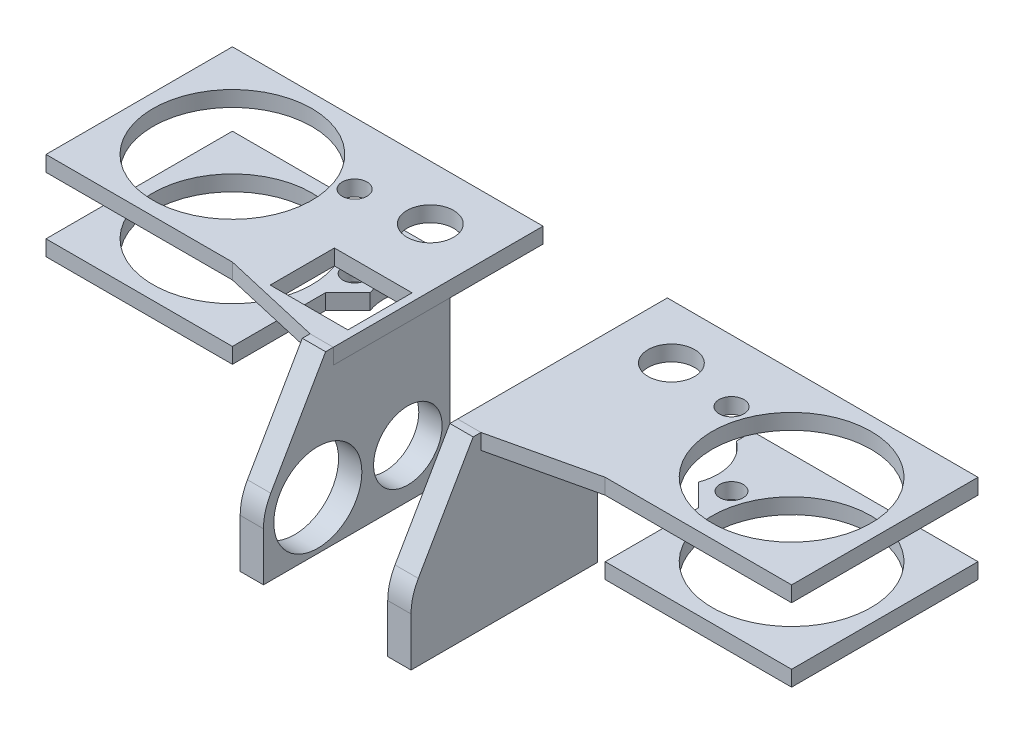
SolidWorks part; units mm, degrees
material "Alum Plate"
ref_plane "Front Plane" through (0, 0, 0) normal (0, 0, 1) x (1, 0, 0)
ref_plane "Top Plane" through (0, 0, 0) normal (0, 1, 0) x (1, 0, 0)
ref_plane "Right Plane" through (0, 0, 0) normal (1, 0, 0) x (0, 0, -1)
sketch "Sketch1" plane through (0, 0, 0) normal (0, 1, 0) x (1, 0, 0)
  line L0 (0, 0) -> (114.3, 0) construction
  line L1 (-114.3, 0) -> (0, 0) construction
  line L3 (-9.525, 158.75) -> (-3.175, 158.75)
  line L4 (-9.525, 158.75) -> (-9.525, 44.45)
  line L5 (-9.525, 44.45) -> (-3.175, 44.45)
  line L6 (-3.175, 158.75) -> (-3.175, 44.45)
  line L7 (-9.525, 158.75) -> (-3.175, 44.45) construction
  line L8 (-9.525, 44.45) -> (-3.175, 158.75) construction
  line L14 (-152.4, -76.2) -> (152.4, -76.2)
  line L18 (-114.3, 0) -> (-49.2756, 15.875) construction
  line L19 (49.2756, 15.875) -> (114.3, 0) construction
  line L20 (-25.4, 38.1) -> (0, 38.1) construction
  line L21 (-6.35, 101.6) -> (0, 101.6)
  line L29 (0, 0) -> (0, -25.4) construction
  line L30 (-114.3, 0) -> (-77.0346, 12.7) construction
  line L43 (-77.0346, 12.7) -> (-49.2756, 15.875) construction
  line L44 (49.2756, 15.875) -> (77.0346, 12.7) construction
  line L55 (77.0346, 12.7) -> (114.3, 0) construction
  line L69 (-152.4, -76.2) -> (-152.4, 38.1)
  line L70 (-152.4, 38.1) -> (152.4, 38.1)
  line L71 (152.4, -76.2) -> (152.4, 38.1)
  line L78 (0, 101.6) -> (0, -25.4)
  line L79 (0, -25.4) -> (0, -152.4) construction
  line L80 (-9.525, -209.55) -> (-3.175, -209.55) construction
  line L81 (-9.525, -209.55) -> (-9.525, -95.25) construction
  line L82 (-9.525, -95.25) -> (-3.175, -95.25) construction
  line L83 (-3.175, -209.55) -> (-3.175, -95.25) construction
  line L84 (-9.525, -209.55) -> (-3.175, -95.25) construction
  line L85 (-9.525, -95.25) -> (-3.175, -209.55) construction
  line L86 (0, -152.4) -> (-6.35, -152.4) construction
  line L87 (-34.925, -76.2) -> (-25.4, -76.2)
  line L88 (-34.925, -76.2) -> (-34.925, 38.1)
  line L89 (-34.925, 38.1) -> (-25.4, 38.1)
  line L90 (-25.4, -76.2) -> (-25.4, 38.1)
  line L91 (34.925, -76.2) -> (25.4, -76.2)
  line L92 (34.925, -76.2) -> (34.925, 38.1)
  line L93 (34.925, 38.1) -> (25.4, 38.1)
  line L94 (25.4, -76.2) -> (25.4, 38.1)
  line L95 (0, 38.1) -> (25.4, 38.1) construction
  circle A0 centre (-114.3, 0) radius 32.5
  circle A1 centre (-114.3, 0) radius 25
  circle A2 centre (114.3, 0) radius 32.5
  circle A3 centre (114.3, 0) radius 25
  circle A4 centre (-49.2756, 15.875) radius 17.5006
  circle A5 centre (49.2756, 15.875) radius 17.5006
  circle A6 centre (-77.0346, 12.7) radius 22.86
  circle A7 centre (77.0346, 12.7) radius 22.86
  point P8 (-6.35, 101.6)
  point P21 (114.3, 32.5)
  point P25 (49.2756, 33.3756)
  point P29 (49.2756, -1.6256)
  point P31 (0, -76.2)
  point P32 (-6.35, -152.4)
  point P62 (146.8, 0)
  dimension "D1" = 50
  dimension "D2" = 65
  dimension "D8" = 35.0012
  dimension "D11" = 127
  dimension "D12" = 63.5
  dimension "D17" = 45.72
  dimension "D3" = 114.3
  dimension "D4" = 6.35
  dimension "D5" = 228.6
  dimension "D6" = 38.1
  dimension "D7" = 38.1
  dimension "D9" = 114.3
  dimension "D10" = 9.525
  dimension "D13" = 9.525
  dimension "D14" = 50.8
  dimension "D15" = 27.94
  dimension "D16" = 39.37
  dimension "D18" = 22.225
  dimension "D19" = 25.4
sketch "Sketch2" plane through (0, 0, 0) normal (1, 0, 0) x (0, 0, -1)
  line L0 (0, 22.225) -> (0, 49.825) construction
  line L1 (-32.5, 53.325) -> (32.5, 53.325)
  line L2 (-32.5, 53.325) -> (-32.5, 46.325)
  line L3 (-32.5, 46.325) -> (32.5, 46.325)
  line L4 (32.5, 53.325) -> (32.5, 46.325)
  line L5 (-32.5, 53.325) -> (32.5, 46.325) construction
  line L6 (-32.5, 46.325) -> (32.5, 53.325) construction
  line L7 (-32.5, 82.55) -> (32.5, 82.55)
  line L8 (-32.5, 82.55) -> (-32.5, 75.55)
  line L9 (-32.5, 75.55) -> (32.5, 75.55)
  line L10 (32.5, 82.55) -> (32.5, 75.55)
  line L11 (-32.5, 82.55) -> (32.5, 75.55) construction
  line L12 (-32.5, 75.55) -> (32.5, 82.55) construction
  line L13 (-25.8191, 0) -> (33.9817, 0) construction
  line L14 (-25.4, 63.5) -> (-152.4, 63.5)
  line L15 (-76.2, 82.55) -> (38.1, 82.55)
  line L16 (-76.2, 82.55) -> (-76.2, 46.325)
  line L17 (-76.2, 46.325) -> (38.1, 46.325)
  line L18 (38.1, 82.55) -> (38.1, 46.325)
  line L19 (-17.175, 32.5662) -> (-53.975, 32.5662) construction
  line L20 (-53.975, 32.5662) -> (-25.4, 63.5) construction
  line L21 (101.6, 0) -> (-25.4, 0) construction
  line L22 (-76.2, 76.2) -> (38.1, 76.2)
  line L23 (-76.2, 52.675) -> (38.1, 52.675)
  line L24 (-17.175, 32.5662) -> (-25.4, 63.5) construction
  line L25 (-3.175, 32.5662) -> (-3.175, 75.55) construction
  line L32 (-76.2, 12.7) -> (38.1, 12.7)
  line L33 (-76.2, 12.7) -> (-76.2, 9.525)
  line L38 (-76.2, 9.525) -> (38.1, 9.525)
  line L39 (38.1, 12.7) -> (38.1, 9.525)
  line L40 (-1.6256, 31.6992) -> (33.3756, 31.6992)
  line L41 (-1.6256, 31.6992) -> (-1.6256, 76.2)
  line L42 (-1.6256, 76.2) -> (33.3756, 76.2)
  line L43 (33.3756, 31.6992) -> (33.3756, 76.2)
  line L44 (-1.6256, 31.6992) -> (33.3756, 76.2) construction
  line L45 (-1.6256, 76.2) -> (33.3756, 31.6992) construction
  line L46 (-38.1, 82.55) -> (-38.1, 46.325)
  line L47 (-38.1, 64.4375) -> (0, 64.4375) construction
  line L48 (0, 64.4375) -> (38.1, 64.4375) construction
  line L49 (-76.2, 12.7) -> (38.1, 9.525) construction
  line L50 (-76.2, 9.525) -> (38.1, 12.7) construction
  circle A0 centre (0, 22.225) radius 22.225
  circle A1 centre (-25.4, 63.5) radius 18.0086
  circle A2 centre (-17.175, 32.5662) radius 14
  circle A3 centre (-152.4, 63.5) radius 57.15
  circle A4 centre (-25.4, 63.5) radius 4.7625
  circle A5 centre (-53.975, 32.5662) radius 18
  point P2 (0, 49.825)
  point P8 (0, 79.05)
  point P16 (-35.975, 32.5662)
  point P28 (-71.975, 32.5662)
  point P32 (15.875, 53.9496)
  point P34 (-209.55, 63.5)
  point P35 (-31.175, 32.5662)
  point P36 (-3.175, 32.5662)
  point P37 (-7.3914, 63.5)
  point P38 (-43.4086, 63.5)
  point P57 (-19.05, 11.1125)
  dimension "D1" = 44.45
  dimension "D8" = 36.0172
  dimension "D2" = 28
  dimension "D11" = 9.525
  dimension "D12" = 36
  dimension "D3" = 7
  dimension "D4" = 82.55
  dimension "D5" = 22.225
  dimension "D6" = 6.35
  dimension "D7" = 6.35
  dimension "D9" = 63.5
  dimension "D10" = 44.5008
  dimension "D13" = 19.05
  dimension "D14" = 28.575
  dimension "D15" = 3.175
  dimension "D16" = 50.8
sketch "Sketch5" plane through (0, 0, 0) normal (0, 1, 0) x (1, 0, 0)
  line L0 (-34.925, -76.2) -> (-34.925, 38.1) construction
  line L1 (-60.071, -3.175) -> (-28.575, -3.175)
  line L2 (-60.071, -3.175) -> (-60.071, -31.175)
  line L3 (-60.071, -31.175) -> (-28.575, -31.175)
  line L4 (-28.575, -3.175) -> (-28.575, -31.175)
  line L5 (-60.071, -3.175) -> (-28.575, -31.175) construction
  line L6 (-60.071, -31.175) -> (-28.575, -3.175) construction
  line L7 (-74.93, -35.975) -> (-34.925, -35.975)
  line L8 (-74.93, -35.975) -> (-74.93, -71.975)
  line L9 (-74.93, -71.975) -> (-34.925, -71.975)
  line L10 (-34.925, -35.975) -> (-34.925, -71.975)
  line L11 (-74.93, -35.975) -> (-34.925, -71.975) construction
  line L12 (-74.93, -71.975) -> (-34.925, -35.975) construction
  line L13 (-60.071, -7.3914) -> (-20.066, -7.3914)
  line L14 (-60.071, -7.3914) -> (-60.071, -43.4086)
  line L15 (-60.071, -43.4086) -> (-20.066, -43.4086)
  line L16 (-20.066, -7.3914) -> (-20.066, -43.4086)
  line L17 (-60.071, -7.3914) -> (-20.066, -43.4086) construction
  line L18 (-60.071, -43.4086) -> (-20.066, -7.3914) construction
  line L20 (-25.4, -76.2) -> (-25.4, 38.1) construction
  point P0 (-44.323, -17.175)
  point P5 (-54.9275, -53.975)
  point P10 (-40.0685, -25.4)
  point P15 (-25.4, -3.175)
  point P16 (-29.3548, -3.175)
  dimension "D1" = 3.175
  dimension "D2" = 31.496
  dimension "D5" = 40.005
  dimension "D6" = 40.005
ref_plane "Plane1" through (0, 76.2, 0) normal (0, 1, 0) x (1, 0, 0)
ref_plane "Plane2" through (0, 52.675, 0) normal (0, -1, 0) x (-1, 0, 0)
ref_plane "Plane3" through (25.4, 0, 0) normal (1, 0, 0) x (0, 0, -1)
sketch "Sketch6" plane through (25.4, 0, 0) normal (1, 0, 0) x (0, 0, -1)
  line L2 (-73.2267, 43.6713) -> (-50.8, 82.55)
  line L3 (-76.2, 82.55) -> (38.1, 82.55) construction
  line L4 (-50.8, 82.55) -> (-47.625, 82.55)
  line L5 (-47.625, 82.55) -> (-47.625, 76.2)
  line L6 (-76.2, 76.2) -> (38.1, 76.2) construction
  line L7 (-47.625, 76.2) -> (0, 76.2)
  line L8 (0, 76.2) -> (0, 12.7)
  line L10 (-76.2, 12.7) -> (38.1, 12.7) construction
  line L11 (-76.2, 12.7) -> (-76.2, 32.5662)
  line L12 (-76.2, 12.7) -> (0, 12.7)
  arc A3 (-76.2, 32.5662) -> (-73.2267, 43.6713) centre (-53.975, 32.5662) cw
  point P7 (-73.8749, 40.41)
  dimension "D1" = 25.4
  dimension "D2" = 22.225
  dimension "D3" = 3.175
extrude "Boss-Extrude1" add sketch "Sketch6" along normal up to vertex (9.525 mm away) up to point (34.925, 0, -38.1)
sketch "Sketch7" plane through (0, 76.2, 0) normal (0, 1, 0) x (1, 0, 0)
  line L0 (25.4, -47.625) -> (34.925, -47.625)
  line L2 (152.4, -76.2) -> (152.4, 38.1) construction
  line L3 (152.4, -38.1) -> (152.4, 38.1)
  line L4 (152.4, 38.1) -> (25.4, 38.1)
  line L5 (25.4, 38.1) -> (25.4, -47.625)
  line L6 (152.4, -38.1) -> (76.2, -38.1)
  line L7 (76.2, -38.1) -> (34.925, -47.625)
  line L8 (114.3, 38.1) -> (114.3, 0) construction
  line L9 (114.3, 0) -> (114.3, -38.1) construction
  circle A0 centre (114.3, 0) radius 32.5 construction
  circle A1 centre (114.3, 0) radius 32.5
  circle A2 centre (77.0346, 12.7) radius 5.08
  circle A3 centre (49.2756, 15.875) radius 9.525
  dimension "D1" = 10.16
  dimension "D2" = 19.05
extrude "Boss-Extrude2" add sketch "Sketch7" along normal up to surface (6.35 mm away) separate body up to face at (30.1625, 82.55, 49.2125)
sketch "Sketch8" plane through (0, 52.675, 0) normal (0, -1, 0) x (-1, 0, 0)
  line L0 (-60.325, 31.3932) -> (-60.325, 38.1)
  line L1 (-76.2, -38.1) -> (-152.4, -38.1)
  line L2 (-76.2, -38.1) -> (-76.2, 38.1) construction
  line L3 (-76.2, 38.1) -> (-152.4, 38.1)
  line L4 (-152.4, -38.1) -> (-152.4, 38.1)
  line L5 (-76.2, -38.1) -> (-152.4, 38.1) construction
  line L6 (-76.2, 38.1) -> (-152.4, -38.1) construction
  line L7 (152.4, 38.1) -> (-152.4, 38.1) construction
  line L8 (-60.325, 38.1) -> (-76.2, 38.1)
  line L9 (-76.2, -38.1) -> (-76.2, 0)
  line L10 (-76.2, 0) -> (-67.0856, 9.1144)
  line L11 (-34.925, -76.2) -> (-34.925, 38.1) construction
  circle A0 centre (-114.3, 0) radius 32.5 construction
  circle A1 centre (-114.3, 0) radius 32.5
  arc A2 (-67.0856, 9.1144) -> (-60.325, 31.3932) centre (-49.2756, 15.875) cw
  circle A3 centre (-77.0346, 12.7) radius 4.7625
  dimension "D1" = 9.525
  dimension "D2" = 19.05
  dimension "D3" = 25.4
  dimension "D4" = 45
  dimension "D5" = 38.1
extrude "Boss-Extrude3" add sketch "Sketch8" along normal up to vertex (6.35 mm away) separate body up to point (0, 46.325, -38.1)
mirror "Mirror2" about plane through (0, 0, 0) normal (1, 0, 0) of bodies 106 108 111
sketch "Sketch10" plane through (-25.4, 0, 0) normal (1, 0, 0) x (0, 0, -1)
  circle A0 centre (-53.975, 32.5662) radius 18 construction
  circle A1 centre (-53.975, 32.5662) radius 18
  circle A2 centre (-17.175, 32.5662) radius 14 construction
  circle A3 centre (-17.175, 32.5662) radius 14
extrude "Cut-Extrude2" cut sketch "Sketch10" against normal through all
sketch "Sketch11" plane through (-34.925, 0, 0) normal (-1, 0, 0) x (0, 0, 1)
  circle A1 centre (25.4, 63.5) radius 18.2626
  circle A4 centre (25.4, 63.5) radius 18.0086 construction
  point P4 (0, 0)
  dimension "D1" = 0.254
extrude "Cut-Extrude6" cut sketch "Sketch11" against normal offset from surface (6.35 mm away) 3.175 up to face at (-25.4, 32.5662, 35.975)
sketch "Sketch12" plane through (0, 76.2, 0) normal (0, -1, 0) x (1, 0, 0)
  line L0 (-60.071, 7.3914) -> (-60.071, 43.4086) construction
  line L1 (-28.575, 12.2763) -> (-60.325, 12.2763)
  line L2 (-28.575, 12.2763) -> (-28.575, 38.5237)
  line L3 (-28.575, 38.5237) -> (-60.325, 38.5237)
  line L4 (-60.325, 12.2763) -> (-60.325, 38.5237)
  line L5 (-28.575, 12.2763) -> (-60.325, 38.5237) construction
  line L6 (-28.575, 38.5237) -> (-60.325, 12.2763) construction
  point P4 (-44.45, 25.4)
  point P6 (0, 0)
  point P8 (-67.0844, 12.2763)
  dimension "D1" = 0.254
extrude "Cut-Extrude7" cut sketch "Sketch12" against normal through all
